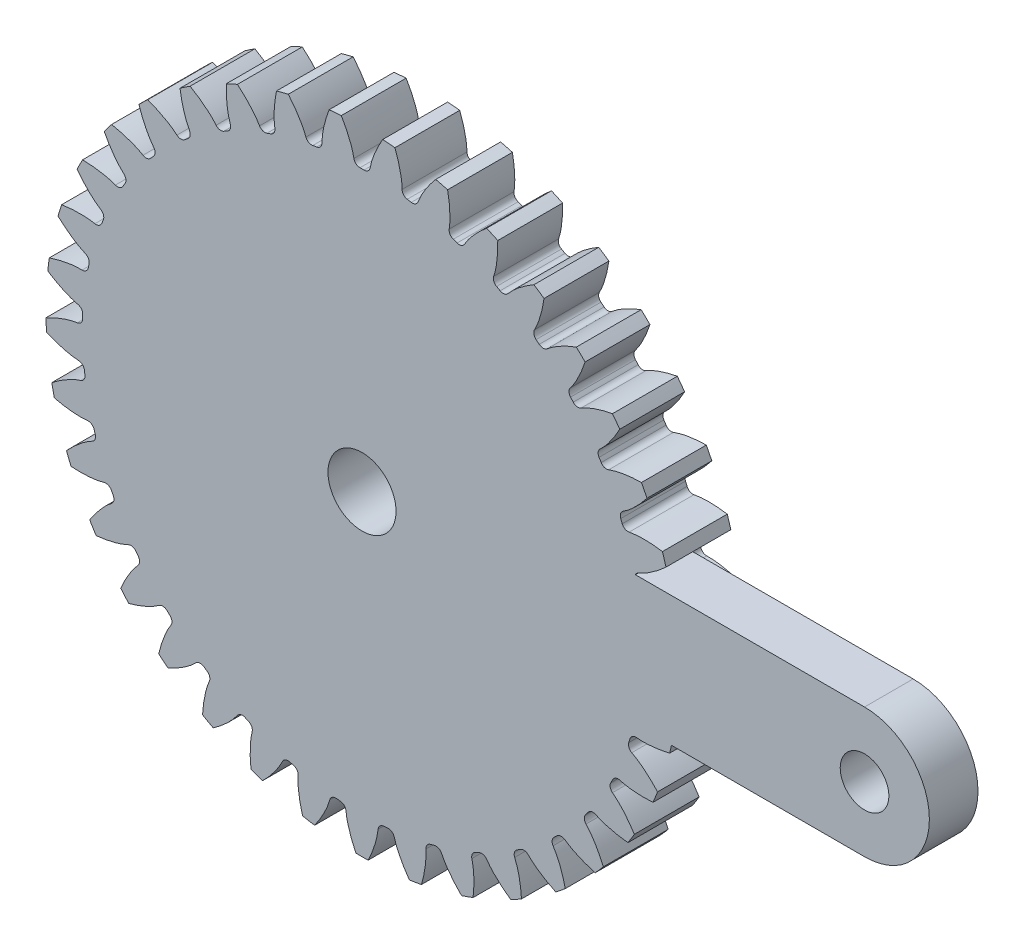
SolidWorks part; units mm, degrees
material "Vero PureWhite"
ref_plane "前视基准面" through (0, 0, 0) normal (0, 0, 1) x (1, 0, 0)
ref_plane "上视基准面" through (0, 0, 0) normal (0, 1, 0) x (1, 0, 0)
ref_plane "右视基准面" through (0, 0, 0) normal (1, 0, 0) x (0, 0, -1)
other "Configuration Table"
ref_axis "Axis1" through (0, 0, -88.99) along (0, 0, 1)
sketch "草图1" plane through (0, 0, 0) normal (0, 0, 1) x (1, 0, 0)
  circle A0 centre (0, 0) radius 19.5
extrude "LaShenA" add sketch "草图1" along normal blind 4
sketch "SketchA" plane through (0, 0, 4) normal (0, 0, 1) x (1, 0, 0)
  line L0 (0, 0) -> (0, 19.5) construction
  arc A0 (0.1249, 17.2495) -> (-0.1249, 17.2495) centre (0, 0) ccw
  arc A1 (1.6316, 20.0089) -> (-1.6316, 20.0089) centre (0, 0) ccw
  arc A2 (-0.1249, 17.2495) -> (-0.5007, 17.5572) centre (-0.1277, 17.6295) cw
  arc A3 (0.5007, 17.5572) -> (0.1249, 17.2495) centre (0.1277, 17.6295) cw
  circle A4 centre (0, 0) radius 17.3843 construction
  circle A5 centre (0, 0) radius 19.5 construction
  circle A6 centre (0, 0) radius 17.25 construction
  circle A7 centre (0, 0) radius 18.5 construction
  spline S0 degree 3 poles (0.5007, 17.5572) (0.5047, 17.5775) (0.5148, 17.6293) (0.5294, 17.6986) (0.5455, 17.7663) (0.5598, 17.8228) (0.576, 17.8829) (0.5942, 17.9466) (0.6146, 18.0138) (0.6372, 18.0846) (0.6621, 18.1588) (0.6895, 18.2365) (0.7195, 18.3174) (0.7521, 18.4017) (0.7876, 18.4892) (0.8259, 18.5798) (0.8672, 18.6735) (0.9116, 18.7702) (0.9592, 18.8699) (1.0101, 18.9724) (1.0644, 19.0777) (1.1222, 19.1857) (1.1835, 19.2963) (1.2486, 19.4095) (1.3174, 19.5251) (1.39, 19.6431) (1.4936, 19.8057) (1.5752, 19.9275) (1.6316, 20.0089) knots 0.105238 0.105238 0.105238 0.105238 0.125626 0.157343 0.175185 0.194349 0.214835 0.236643 0.259774 0.284226 0.31 0.337096 0.365514 0.395255 0.426317 0.458701 0.492408 0.527436 0.563786 0.601458 0.640453 0.680769 0.722408 0.765368 0.80965 0.855255 0.902181 1 1 1 1
  spline S1 degree 3 poles (-0.5007, 17.5572) (-0.5047, 17.5775) (-0.5148, 17.6293) (-0.5294, 17.6986) (-0.5455, 17.7663) (-0.5598, 17.8228) (-0.576, 17.8829) (-0.5942, 17.9466) (-0.6146, 18.0138) (-0.6372, 18.0846) (-0.6621, 18.1588) (-0.6895, 18.2365) (-0.7195, 18.3174) (-0.7521, 18.4017) (-0.7876, 18.4892) (-0.8259, 18.5798) (-0.8672, 18.6735) (-0.9116, 18.7702) (-0.9592, 18.8699) (-1.0101, 18.9724) (-1.0644, 19.0777) (-1.1222, 19.1857) (-1.1835, 19.2963) (-1.2486, 19.4095) (-1.3174, 19.5251) (-1.39, 19.6431) (-1.4936, 19.8057) (-1.5752, 19.9275) (-1.6316, 20.0089) knots 0.105238 0.105238 0.105238 0.105238 0.125626 0.157343 0.175185 0.194349 0.214835 0.236643 0.259774 0.284226 0.31 0.337096 0.365514 0.395255 0.426317 0.458701 0.492408 0.527436 0.563786 0.601458 0.640453 0.680769 0.722408 0.765368 0.80965 0.855255 0.902181 1 1 1 1
  dimension "D1" = 0.38
  dimension "Db" = 34.7686
  dimension "Da" = 39
  dimension "Df" = 34.5
  dimension "Dn" = 37
extrude "Cut-ExtrudeA" cut sketch "SketchA" against normal blind 10
pattern_circular "www.KYTool.cn" count 37 over 360 about axis through (0, 0, -88.99) along (0, 0, 1) of "Cut-ExtrudeA"
sketch "草图2" plane through (0, 0, 4) normal (0, 0, 1) x (1, 0, 0)
  line L0 (0, 0) -> (31, 0) construction
  line L1 (0, 4) -> (31, 4)
  line L2 (0, -4) -> (31, -4)
  arc A0 (0, 4) -> (0, -4) centre (0, 0) ccw
  arc A1 (31, -4) -> (31, 4) centre (31, 0) ccw
  point P4 (15.5, 0)
  dimension "D2" = 4
  dimension "D1" = 31
extrude "凸台-拉伸1" add sketch "草图2" against normal blind 3
sketch "草图3" plane through (0, 0, 1) normal (0, 0, -1) x (-1, 0, 0)
  circle A0 centre (-31, 0) radius 1.5
  dimension "D1" = 3
extrude "切除-拉伸1" cut sketch "草图3" against normal through all
sketch "草图4" plane through (0, 0, 0) normal (0, 0, -1) x (-1, 0, 0)
  circle A0 centre (0, 0) radius 2.1
  dimension "D1" = 4.2
extrude "切除-拉伸2" cut sketch "草图4" against normal through all
